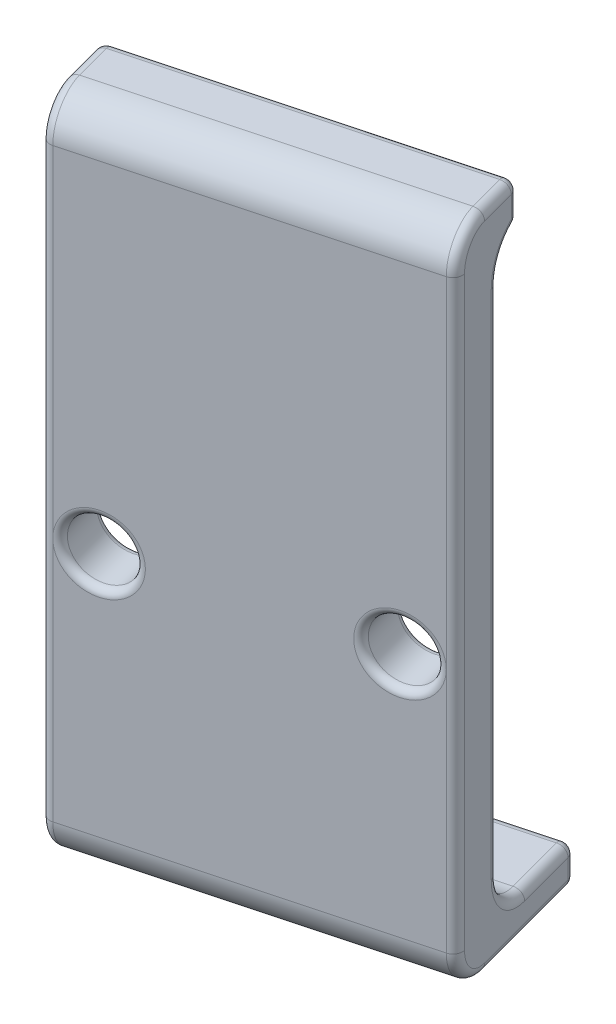
SolidWorks part; units mm, degrees
ref_plane "Front Plane" through (0, 0, 0) normal (1, 0, 0) x (0, 1, 0)
ref_plane "Top Plane" through (0, 0, 0) normal (0, 0, 1) x (0, 1, 0)
ref_plane "Right Plane" through (0, 0, 0) normal (0, 1, 0) x (-1, 0, 0)
sketch "Sketch1" plane through (-4.4587, 0, -16.6399) normal (0.2588, 0, 0.9659) x (0.9659, 0, -0.2588)
  line L0 (-63.6, -11.75) -> (-63.6, 8.25)
  line L1 (-63.6, -9.25) -> (-63.6, 16.35) construction
  line L2 (-45.6, -11.75) -> (-45.6, 8.25)
  line L3 (-45.6, -9.25) -> (-45.6, 16.35) construction
  line L4 (-45.6, 8.25) -> (-63.6, 8.25)
  line L5 (-63.6, -11.75) -> (-63.6, -26.75)
  line L6 (-45.6, -11.75) -> (-45.6, -26.75)
  line L7 (-63.6, -26.75) -> (-45.6, -26.75)
  line L8 (-63.6, -24.75) -> (-45.6, -24.75)
  line L9 (-63.6, 6.25) -> (-45.6, 6.25)
  arc A0 (-61.1, -9.25) -> (-63.6, -11.75) centre (-61.1, -11.75) ccw construction
  arc A1 (-45.6, -11.75) -> (-48.1, -9.25) centre (-48.1, -11.75) ccw construction
  circle A2 centre (-61.1, -11.75) radius 1.6
  circle A3 centre (-48.1, -11.75) radius 1.6
  circle A4 centre (-61.1, -11.75) radius 1.9 construction
  circle A5 centre (-48.1, -11.75) radius 1.9 construction
  dimension "D1" = 20
  dimension "D2" = 15
  dimension "D3" = 3.2
  dimension "D4" = 2
  dimension "D5" = 2
extrude "Boss-Extrude1" add sketch "Sketch1" along normal blind 3 contours L8 L5 L7 L6 | A2 | A3 | L7 L6 L2 L4 L0 L5 region at (-57.1982, -25.75, -2.5084)
extrude "Boss-Extrude2" add sketch "Sketch1<3>" against normal up to surface (5.75 mm away) contours L8 L5 L7 L6 region at (-57.1982, -25.75, -2.5084)
sketch "Sketch1<3>" plane through (-4.4587, 0, -16.6399) normal (0.2588, 0, 0.9659) x (0.9659, 0, -0.2588) same geometry as "Sketch1"
extrude "Boss-Extrude3" add sketch "Sketch1<4>" against normal blind 1.5 contours L0 L9 L2 L4 region at (-57.1982, 7.25, -2.5084)
sketch "Sketch1<4>" plane through (-4.4587, 0, -16.6399) normal (0.2588, 0, 0.9659) x (0.9659, 0, -0.2588) same geometry as "Sketch1"
fillet "Fillet1" radius 2 4 edges at (-57.1982, 6.25, -2.5084) (-56.4218, 8.25, 0.3894) (-56.4218, -26.75, 0.3894) (-57.1982, -24.75, -2.5084)
fillet "Fillet2" radius 0.5 26 edges at (-66.8945, -24.75, -3.922) (-49.5078, -24.75, -8.5808) (-66.5062, -26.75, -2.4731) (-49.1196, -26.75, -7.1319) (-48.5696, 8.25, -5.0793) (-47.88, 7.6642, -2.5058) (-47.7284, -9.25, -1.94) (-47.88, -26.1642, -2.5058) (-48.6133, 5.5383, -5.2424) (-48.5049, -9.2182, -4.8378) (-48.6565, -24.1642, -5.4036) (-65.9999, 5.5383, -0.5836) (-65.8915, -9.2182, -0.179) (-66.0432, -24.1642, -0.7449) (-65.9562, 8.25, -0.4205) (-65.2667, 7.6642, 2.1529) (-65.1151, -9.25, 2.7187) (-65.2667, -26.1642, 2.1529) (-66.2798, 7.25, -1.6279) (-57.5864, 8.25, -3.9573) (-48.8931, 7.25, -6.2867) (-57.5864, 6.25, -3.9573) (-67.3797, -25.75, -5.7331) (-58.6864, -24.75, -8.0625) (-49.9931, -25.75, -10.3919) (-58.6864, -26.75, -8.0625)
fillet "Fillet3" radius 0.4 4 edges at (-61.9312, -11.75, -1.2402) (-49.3742, -11.75, -4.6049) (-48.5978, -11.75, -1.7071) (-61.1548, -11.75, 1.6576)
